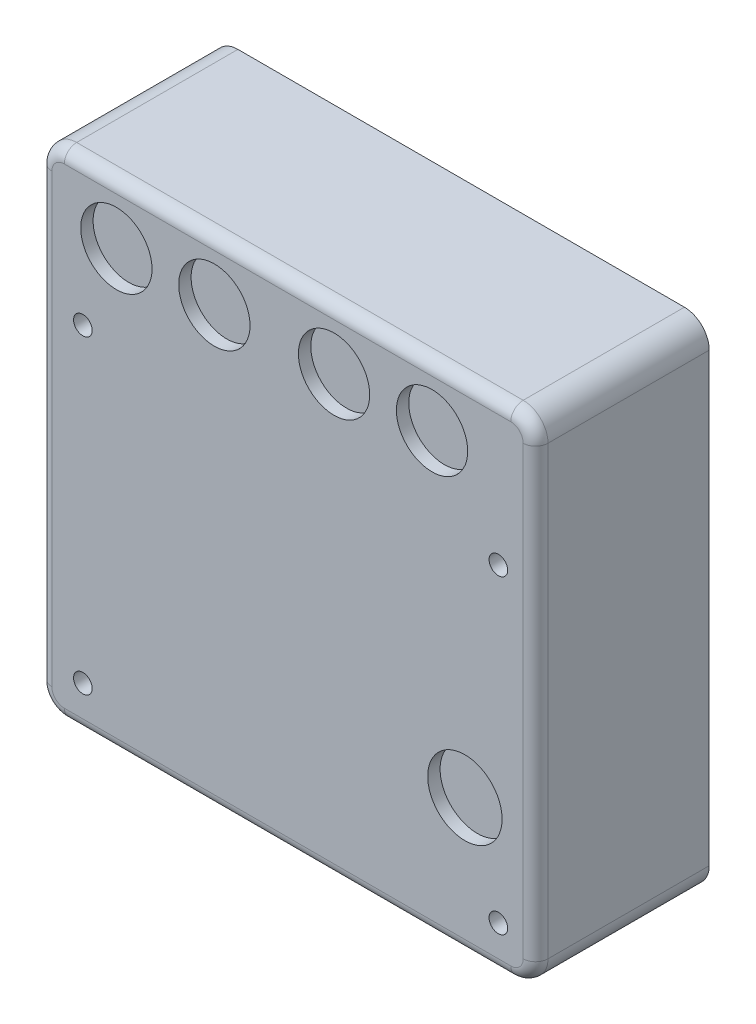
SolidWorks part; units mm, degrees
ref_plane "Front Plane" through (0, 0, 0) normal (0, 0, 1) x (1, 0, 0)
ref_plane "Top Plane" through (0, 0, 0) normal (0, 1, 0) x (1, 0, 0)
ref_plane "Right Plane" through (0, 0, 0) normal (1, 0, 0) x (0, 0, -1)
sketch "Sketch1" plane through (0, 0, 0) normal (0, 0, 1) x (1, 0, 0)
  line L1 (-40, 40) -> (40, 40)
  line L2 (-40, 40) -> (-40, -40)
  line L3 (-40, -40) -> (40, -40)
  line L4 (40, 40) -> (40, -40)
  line L5 (-40, 40) -> (40, -40) construction
  line L6 (-40, -40) -> (40, 40) construction
  point P0 (0, 0)
  dimension "D1" = 80
  dimension "D2" = 80
extrude "Boss-Extrude1" add sketch "Sketch1" along normal mid plane 28
fillet "Fillet1" radius 2 4 edges at (40, 0, 14) (0, -40, 14) (-40, 0, 14) (0, 40, 14)
fillet "Fillet2" radius 4 8 edges at (-39.4142, 39.4142, 13.4142) (39.4142, 39.4142, 13.4142) (-39.4142, -39.4142, 13.4142) (39.4142, -39.4142, 13.4142) (40, -40, -1) (-40, -40, -1) (40, 40, -1) (-40, 40, -1)
sketch "Sketch2" plane through (0, 0, 14) normal (0, 0, 1) x (1, 0, 0)
  line L0 (-27.6, 30.4) -> (-11.8, 30.4) construction
  line L1 (-11.8, 30.4) -> (7.5, 30.4) construction
  line L2 (7.5, 30.4) -> (23.3, 30.4) construction
  line L3 (-36, 40) -> (36, 40) construction
  line L4 (-40, -36) -> (-40, 36) construction
  circle A0 centre (-27.6, 30.4) radius 5.75
  circle A1 centre (-11.8, 30.4) radius 5.75
  circle A2 centre (7.5, 30.4) radius 5.75
  circle A3 centre (23.3, 30.4) radius 5.75
  dimension "D1" = 11.5
  dimension "D4" = 19.3
  dimension "D5" = 12.4
  dimension "D2" = 9.6
  dimension "D3" = 15.8
extrude "Cut-Extrude1" cut sketch "Sketch2" against normal blind 2
sketch "Sketch3" plane through (0, 0, 14) normal (0, 0, 1) x (1, 0, 0)
  line L0 (-40, -36) -> (-40, 36) construction
  line L1 (-33, 17) -> (34, 17) construction
  line L2 (-33, 17) -> (-33, -33) construction
  line L3 (-33, -33) -> (34, -33) construction
  line L4 (34, 17) -> (34, -33) construction
  line L5 (36, -40) -> (-36, -40) construction
  circle A0 centre (-33, 17) radius 1.5
  circle A2 centre (34, 17) radius 1.5
  circle A3 centre (-33, -33) radius 1.5
  circle A4 centre (34, -33) radius 1.5
  dimension "D5" = 3
  dimension "D1" = 50
  dimension "D2" = 67
  dimension "D3" = 7
  dimension "D4" = 7
extrude "Cut-Extrude2" cut sketch "Sketch3" against normal blind 12
sketch "Sketch6" plane through (0, 0, 14) normal (0, 0, 1) x (1, 0, 0)
  circle A0 centre (28.6, -18.2) radius 6
  circle A1 centre (23.3, 30.4) radius 5.75 construction
  circle A2 centre (23.3, 30.4) radius 5.75 construction
  dimension "D1" = 12
  dimension "D2" = 5.3
  dimension "D3" = 48.6
extrude "Cut-Extrude3" cut sketch "Sketch6" against normal blind 2
sketch "Sketch7" plane through (0, 0, -14) normal (0, 0, -1) x (-1, 0, 0)
  line L1 (-16.75, 21) -> (16.75, 21)
  line L2 (-16.75, 21) -> (-16.75, -21)
  line L3 (-16.75, -21) -> (16.75, -21)
  line L4 (16.75, 21) -> (16.75, -21)
  line L5 (-16.75, 21) -> (16.75, -21) construction
  line L6 (-16.75, -21) -> (16.75, 21) construction
  point P0 (0, 0)
  dimension "D1" = 42
  dimension "D2" = 33.5
extrude "Boss-Extrude2" add sketch "Sketch7" along normal blind 2.5
